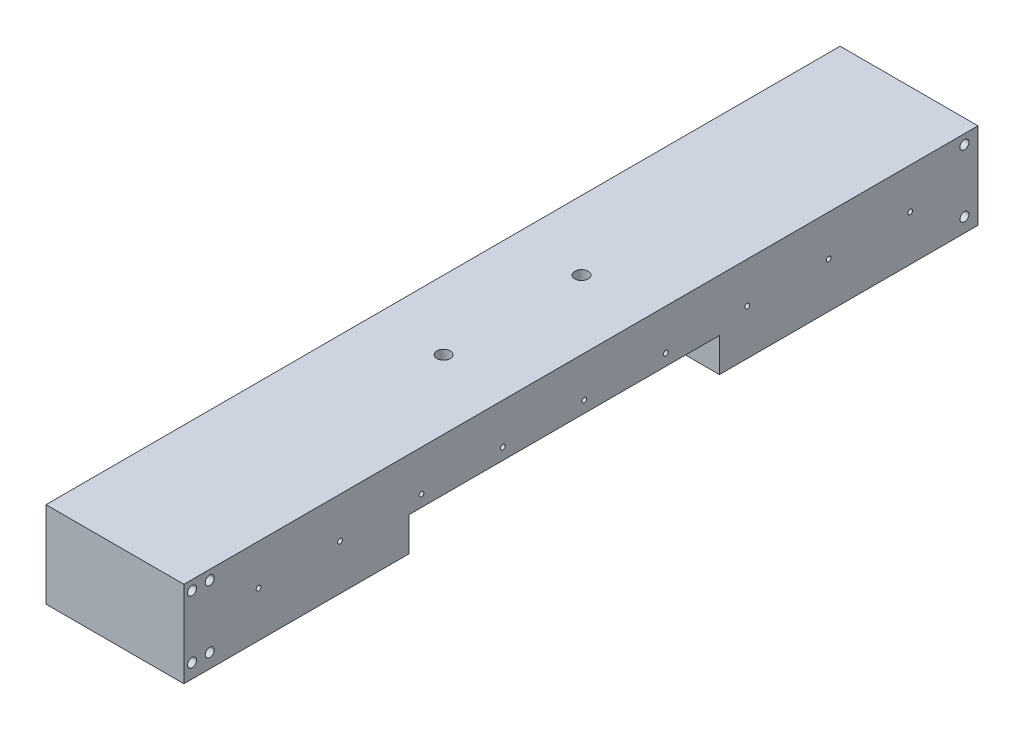
SolidWorks part; units mm, degrees
ref_plane "Front" through (0, 0, 0) normal (0, 0, 1) x (1, 0, 0)
ref_plane "Top" through (0, 0, 0) normal (0, 1, 0) x (1, 0, 0)
ref_plane "Right" through (0, 0, 0) normal (1, 0, 0) x (0, 0, -1)
sketch "Sketch1" plane through (0, 0, 0) normal (0, 0, 1) x (1, 0, 0)
  line L1 (0, 0) -> (101.6, 0)
  line L2 (0, 0) -> (0, 63.5)
  line L3 (0, 63.5) -> (101.6, 63.5)
  line L4 (101.6, 0) -> (101.6, 63.5)
  dimension "D1" = 63.5
  dimension "D2" = 101.6
extrude "Boss-Extrude1" add sketch "Sketch1" along normal blind 585.0001
sketch "Sketch2" plane through (0, 0, 0) normal (-1, 0, 0) x (0, 0, 1)
  line L0 (190.5, 0) -> (190.5, 25)
  line L1 (585.0001, 0) -> (0, 0) construction
  line L2 (190.5, 25) -> (419.1, 25)
  line L3 (419.1, 25) -> (419.1, 0)
  line L4 (419.1, 0) -> (190.5, 0)
  line L5 (0, 63.5) -> (0, 0) construction
  line L6 (393.7, 25) -> (190.5, 25) construction
  point P8 (419.1, 34.3295)
  dimension "D1" = 190.5
  dimension "D3" = 228.6
extrude "Cut-Extrude1" cut sketch "Sketch2" against normal through all
sketch "Sketch5" plane through (0, 0, 0) normal (-1, 0, 0) x (0, 0, 1)
  arc A0 (6.7, 10.5) -> (13.3, 10.5) centre (10, 10.5) ccw construction
  arc A1 (13.3, 10.5) -> (6.7, 10.5) centre (10, 10.5) ccw construction
  arc A2 (6.7, 56.5) -> (13.3, 56.5) centre (10, 56.5) ccw construction
  arc A3 (13.3, 56.5) -> (6.7, 56.5) centre (10, 56.5) ccw construction
  arc A4 (6.7, 10.5) -> (13.3, 10.5) centre (10, 10.5) ccw
  arc A5 (13.3, 10.5) -> (6.7, 10.5) centre (10, 10.5) ccw
  arc A6 (6.7, 56.5) -> (13.3, 56.5) centre (10, 56.5) ccw
  arc A7 (13.3, 56.5) -> (6.7, 56.5) centre (10, 56.5) ccw
  arc A8 (170, 35.25) -> (170, 31.75) centre (170, 33.5) ccw construction
  arc A9 (170, 31.75) -> (170, 35.25) centre (170, 33.5) ccw construction
  arc A10 (110, 31.75) -> (110, 35.25) centre (110, 33.5) ccw construction
  arc A11 (110, 35.25) -> (110, 31.75) centre (110, 33.5) ccw construction
  arc A12 (50, 31.75) -> (50, 35.25) centre (50, 33.5) ccw construction
  arc A13 (50, 35.25) -> (50, 31.75) centre (50, 33.5) ccw construction
  arc A14 (170, 35.25) -> (170, 31.75) centre (170, 33.5) ccw
  arc A15 (170, 31.75) -> (170, 35.25) centre (170, 33.5) ccw
  arc A16 (110, 31.75) -> (110, 35.25) centre (110, 33.5) ccw
  arc A17 (110, 35.25) -> (110, 31.75) centre (110, 33.5) ccw
  arc A18 (50, 31.75) -> (50, 35.25) centre (50, 33.5) ccw
  arc A19 (50, 35.25) -> (50, 31.75) centre (50, 33.5) ccw
  arc A20 (530, 31.75) -> (530, 35.25) centre (530, 33.5) ccw construction
  arc A21 (530, 35.25) -> (530, 31.75) centre (530, 33.5) ccw construction
  arc A22 (470, 31.75) -> (470, 35.25) centre (470, 33.5) ccw construction
  arc A23 (470, 35.25) -> (470, 31.75) centre (470, 33.5) ccw construction
  arc A24 (410, 31.75) -> (410, 35.25) centre (410, 33.5) ccw construction
  arc A25 (410, 35.25) -> (410, 31.75) centre (410, 33.5) ccw construction
  arc A26 (350, 31.75) -> (350, 35.25) centre (350, 33.5) ccw construction
  arc A27 (350, 35.25) -> (350, 31.75) centre (350, 33.5) ccw construction
  arc A28 (290, 31.75) -> (290, 35.25) centre (290, 33.5) ccw construction
  arc A29 (290, 35.25) -> (290, 31.75) centre (290, 33.5) ccw construction
  arc A30 (230, 31.75) -> (230, 35.25) centre (230, 33.5) ccw construction
  arc A31 (230, 35.25) -> (230, 31.75) centre (230, 33.5) ccw construction
  arc A32 (530, 31.75) -> (530, 35.25) centre (530, 33.5) ccw
  arc A33 (530, 35.25) -> (530, 31.75) centre (530, 33.5) ccw
  arc A34 (470, 31.75) -> (470, 35.25) centre (470, 33.5) ccw
  arc A35 (470, 35.25) -> (470, 31.75) centre (470, 33.5) ccw
  arc A36 (410, 31.75) -> (410, 35.25) centre (410, 33.5) ccw
  arc A37 (410, 35.25) -> (410, 31.75) centre (410, 33.5) ccw
  arc A38 (350, 31.75) -> (350, 35.25) centre (350, 33.5) ccw
  arc A39 (350, 35.25) -> (350, 31.75) centre (350, 33.5) ccw
  arc A40 (290, 31.75) -> (290, 35.25) centre (290, 33.5) ccw
  arc A41 (290, 35.25) -> (290, 31.75) centre (290, 33.5) ccw
  arc A42 (230, 31.75) -> (230, 35.25) centre (230, 33.5) ccw
  arc A43 (230, 35.25) -> (230, 31.75) centre (230, 33.5) ccw
  arc A44 (582.3, 10.5) -> (575.7, 10.5) centre (579, 10.5) ccw construction
  arc A45 (575.7, 10.5) -> (582.3, 10.5) centre (579, 10.5) ccw construction
  arc A46 (562.7, 10.5) -> (569.3, 10.5) centre (566, 10.5) ccw construction
  arc A47 (569.3, 10.5) -> (562.7, 10.5) centre (566, 10.5) ccw construction
  arc A48 (575.7, 56.5) -> (582.3, 56.5) centre (579, 56.5) ccw construction
  arc A49 (582.3, 56.5) -> (575.7, 56.5) centre (579, 56.5) ccw construction
  arc A50 (562.7, 56.5) -> (569.3, 56.5) centre (566, 56.5) ccw construction
  arc A51 (569.3, 56.5) -> (562.7, 56.5) centre (566, 56.5) ccw construction
  arc A52 (582.3, 10.5) -> (575.7, 10.5) centre (579, 10.5) ccw
  arc A53 (575.7, 10.5) -> (582.3, 10.5) centre (579, 10.5) ccw
  arc A54 (562.7, 10.5) -> (569.3, 10.5) centre (566, 10.5) ccw
  arc A55 (569.3, 10.5) -> (562.7, 10.5) centre (566, 10.5) ccw
  arc A56 (575.7, 56.5) -> (582.3, 56.5) centre (579, 56.5) ccw
  arc A57 (582.3, 56.5) -> (575.7, 56.5) centre (579, 56.5) ccw
  arc A58 (562.7, 56.5) -> (569.3, 56.5) centre (566, 56.5) ccw
  arc A59 (569.3, 56.5) -> (562.7, 56.5) centre (566, 56.5) ccw
extrude "Cut-Extrude4" cut sketch "Sketch5" along normal blind 6.35 from surface contours A32 A33 | A34 A35 | A36 A37 | A38 A39 | A40 A41 | A42 A43 | A15 A14 | A16 A17 | A18 A19 starting at face at (101.6, 22.125, 298.65)
extrude "Cut-Extrude5" cut sketch "Sketch5<3>" along normal blind 25.4 from surface contours A54 A55 | A52 A53 | A56 A57 | A58 A59 | A4 A5 | A6 A7 region at (0, 10.5, 10) region at (0, 56.5, 10) region at (0, 10.5, 579) region at (0, 10.5, 566) region at (0, 56.5, 579) region at (0, 56.5, 566) starting at face at (101.6, 33.5, 531.75)
sketch "Sketch5<3>" plane through (0, 0, 0) normal (-1, 0, 0) x (0, 0, 1) same geometry as "Sketch5"
sketch "Sketch6" plane through (0, 25, 0) normal (0, -1, 0) x (1, 0, 0)
  circle A0 centre (50.8, 342.9) radius 4.9344 construction
  circle A1 centre (50.8, 241.3) radius 4.9344 construction
  circle A2 centre (50.8, 342.9) radius 4.9344
  circle A3 centre (50.8, 241.3) radius 4.9344
extrude "Cut-Extrude6" cut sketch "Sketch6" against normal through all
sketch "Sketch7" plane through (0, 0, 0) normal (-1, 0, 0) x (0, 0, 1)
  arc A0 (525.6376, 38.1067) -> (531.1303, 38.1067) centre (528.384, 39.6999) ccw construction
  arc A1 (525.6376, 41.2931) -> (525.6376, 38.1067) centre (528.384, 39.6999) ccw construction
  arc A2 (531.1303, 41.2931) -> (525.6376, 41.2931) centre (528.384, 39.6999) ccw construction
  arc A3 (531.1303, 38.1067) -> (531.1303, 41.2931) centre (528.384, 39.6999) ccw construction
  arc A4 (525.6376, 38.1067) -> (531.1303, 38.1067) centre (528.384, 39.6999) ccw
  arc A5 (525.6376, 41.2931) -> (525.6376, 38.1067) centre (528.384, 39.6999) ccw
  arc A6 (531.1303, 41.2931) -> (525.6376, 41.2931) centre (528.384, 39.6999) ccw
  arc A7 (531.1303, 38.1067) -> (531.1303, 41.2931) centre (528.384, 39.6999) ccw
  arc A8 (53.5485, 41.2931) -> (48.0559, 41.2931) centre (50.8022, 39.6999) ccw construction
  arc A9 (53.5485, 38.1067) -> (53.5485, 41.2931) centre (50.8022, 39.6999) ccw construction
  arc A10 (48.0559, 38.1067) -> (53.5485, 38.1067) centre (50.8022, 39.6999) ccw construction
  arc A11 (48.0559, 41.2931) -> (48.0559, 38.1067) centre (50.8022, 39.6999) ccw construction
  arc A12 (53.5485, 41.2931) -> (48.0559, 41.2931) centre (50.8022, 39.6999) ccw
  arc A13 (53.5485, 38.1067) -> (53.5485, 41.2931) centre (50.8022, 39.6999) ccw
  arc A14 (48.0559, 38.1067) -> (53.5485, 38.1067) centre (50.8022, 39.6999) ccw
  arc A15 (48.0559, 41.2931) -> (48.0559, 38.1067) centre (50.8022, 39.6999) ccw
extrude "Cut-Extrude7" cut sketch "Sketch7" against normal blind 6.35
